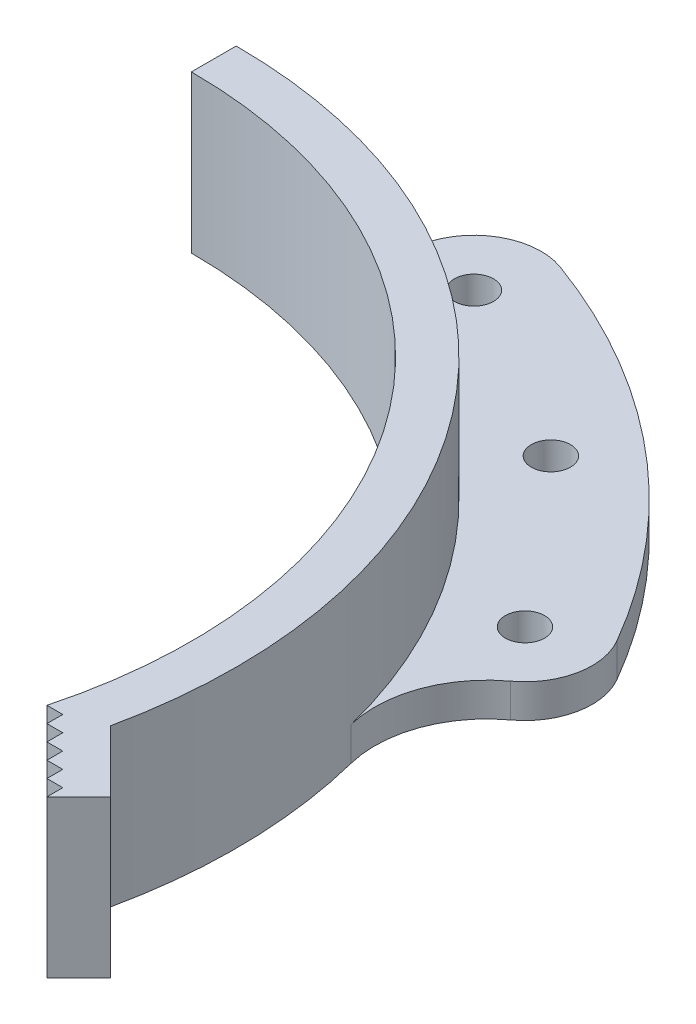
SolidWorks part; units mm, degrees
ref_plane "Спереди" through (0, 0, 0) normal (0, 0, 1) x (1, 0, 0)
ref_plane "Сверху" through (0, 0, 0) normal (0, 1, 0) x (1, 0, 0)
ref_plane "Справа" through (0, 0, 0) normal (1, 0, 0) x (0, 0, -1)
sketch "Эскиз1" plane through (0, 0, 0) normal (0, 1, 0) x (1, 0, 0)
  line L0 (0, 0) -> (18.4691, 50.7434) construction
  line L1 (0, 0) -> (34.7105, 41.3664) construction
  line L2 (0, 0) -> (41.5692, 24) construction
  line L4 (0, 48) -> (0, 52)
  circle A0 centre (34.7105, 41.3664) radius 1.75
  circle A2 centre (18.4691, 50.7434) radius 1.75
  circle A3 centre (46.7654, 27) radius 1.75
  arc A4 (41.5692, 24) -> (51.9615, 30) centre (46.7654, 27) ccw
  arc A5 (41.5692, 24) -> (0, 48) centre (0, 0) ccw construction
  arc A6 (41.5692, 24) -> (0, 48) centre (0, 0) ccw
  arc A8 (20.5212, 56.3816) -> (12.4748, 50.4815) centre (18.4691, 50.7434) ccw
  arc A11 (12.4748, 50.4815) -> (0, 52) centre (0, 0) ccw
  arc A14 (51.9615, 30) -> (20.5212, 56.3816) centre (0, 0) ccw
  point P1 (46.0417, 13.5708)
  point P6 (51.426, 30.7787)
  point P7 (41.4682, 24.1823)
  point P11 (0, 0)
  dimension "D6" = 60
  dimension "D7" = 3
  dimension "D1" = 20
  dimension "D2" = 3.5
  dimension "D4" = 48
  dimension "D5" = 52
  dimension "D8" = 20
extrude "Бобышка-Вытянуть1" add sketch "Эскиз1" along normal blind 3
sketch "Эскиз2" plane through (0, 3, 0) normal (0, 1, 0) x (1, 0, 0)
  line L0 (0, 52) -> (0, 48) construction
  line L1 (49.5718, -18.4591) -> (49.5718, -17.0449)
  line L2 (0, 44) -> (0, 48)
  line L3 (49.5718, -18.4591) -> (52.4002, -15.6307)
  line L4 (49.5718, -18.4591) -> (-11.388, 42.5007) construction
  line L5 (42.5007, -11.388) -> (49.5718, -18.4591) construction
  line L6 (52.4002, -15.6307) -> (46.9155, -10.1459)
  line L7 (49.5718, -17.0449) -> (48.1576, -17.0449)
  line L8 (48.1576, -15.6307) -> (46.7434, -15.6307)
  line L9 (48.1576, -17.0449) -> (48.1576, -15.6307)
  line L10 (46.7434, -14.2165) -> (45.3292, -14.2165)
  line L11 (46.7434, -15.6307) -> (46.7434, -14.2165)
  line L12 (45.3292, -12.8023) -> (43.9149, -12.8023)
  line L13 (45.3292, -14.2165) -> (45.3292, -12.8023)
  line L14 (43.9149, -11.388) -> (42.5007, -11.388)
  line L15 (43.9149, -12.8023) -> (43.9149, -11.388)
  line L16 (0, 0) -> (-11.388, 42.5007) construction
  line L17 (0, 0) -> (0, 44) construction
  arc A0 (42.5007, -11.388) -> (0, 44) centre (0, 0) ccw
  arc A1 (46.9155, -10.1459) -> (0, 48) centre (0, 0) ccw
  arc A2 (41.5692, 24) -> (0, 48) centre (0, 0) ccw construction
  circle A3 centre (0, 0) radius 44 construction
  point P5 (-15.0489, 41.3465)
  point P6 (0, 0)
  dimension "D1" = 4
  dimension "D2" = 15
  dimension "D3" = 1
  dimension "D4" = 1
  dimension "D5" = 5
  dimension "D6" = 4
extrude "Выступ для захвата" add sketch "Эскиз2" along normal blind 11 and the other way blind 3
fillet "Fillet1" radius 10 1 edges at (41.5692, 1.5, -24)
